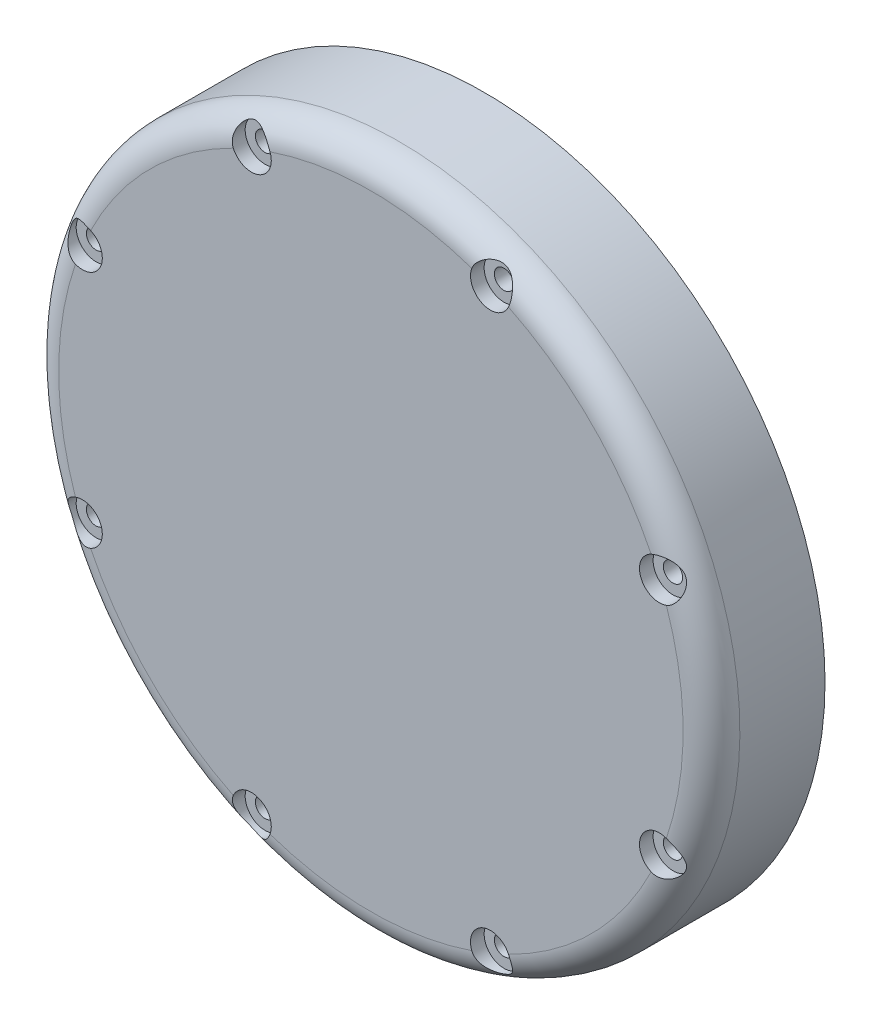
SolidWorks part; units mm, degrees
material "7075-O (SS)"
ref_plane "Front" through (0, 0, 0) normal (0, 0, 1) x (1, 0, 0)
ref_plane "Top" through (0, 0, 0) normal (0, 1, 0) x (1, 0, 0)
ref_plane "Right" through (0, 0, 0) normal (1, 0, 0) x (0, 0, -1)
sketch "Croquis1" plane through (0, 0, 0) normal (0, 0, 1) x (1, 0, 0)
  line L0 (-15, -49.8498) -> (-15, -54.0833)
  line L1 (15, -49.8498) -> (15, -54.0833)
  line L2 (-15, -47.697) -> (15, -47.697) construction
  line L3 (0, -50) -> (0, 50) construction
  arc A0 (18.9474, -56.9298) -> (-18.9474, -56.9298) centre (0, 0) ccw
  arc A1 (16.9811, -47.0281) -> (-16.9811, -47.0281) centre (0, 0) ccw
  arc A2 (15, -54.0833) -> (18.9474, -56.9298) centre (18, -54.0833) ccw
  arc A3 (-15, -54.0833) -> (-18.9474, -56.9298) centre (-18, -54.0833) cw
  arc A4 (15, -49.8498) -> (16.9811, -47.0281) centre (18, -49.8498) cw
  arc A5 (-15, -49.8498) -> (-16.9811, -47.0281) centre (-18, -49.8498) ccw
  point P8 (0, -47.697)
  dimension "D1" = 120
  dimension "D2" = 100
  dimension "D4" = 3
  dimension "D3" = 30
extrude "Saliente-Extruir1" add sketch "Croquis1" along normal blind 15
sketch "Croquis2" plane through (0, 0, 15) normal (0, 0, 1) x (1, 0, 0)
  circle A0 centre (0, 0) radius 60
  dimension "D1" = 120
extrude "Saliente-Extruir2" add sketch "Croquis2" along normal blind 5
hole_wizard "Refrentado para tornillo con cabeza troncocónica de M31" positions "Croquis3" profile "Croquis5" counterbore size "M3" standard "Ansi Metric" end condition up to next
sketch "Croquis3" plane through (0, 0, 20) normal (0, 0, 1) x (1, 0, 0)
  line L1 (-21.0476, -50.8134) -> (21.0476, 50.8134) construction
  line L4 (0, -50) -> (0, 50) construction
  point P4 (21.0476, 50.8134)
  point P18 (50.8134, 21.0476)
  point P19 (50.8134, -21.0476)
  point P20 (21.0476, -50.8134)
  point P21 (-21.0476, -50.8134)
  point P22 (-50.8134, -21.0476)
  point P23 (-50.8134, 21.0476)
  point P24 (-21.0476, 50.8134)
  dimension "D1" = 22.5
  dimension "D2" = 110
  dimension "D3" = 8
sketch "Croquis5" plane through (-21.0476, 50.8134, 20) normal (1, 0, 0) x (0, -1, 0)
  line L0 (0, 0) -> (0, 20)
  line L1 (0, 20) -> (1.7, 20)
  line L3 (1.7, 20) -> (1.7, 2.4)
  line L4 (1.7, 2.4) -> (3.5, 2.4)
  line L5 (3.5, 2.4) -> (3.5, 0)
  line L7 (3.5, 0) -> (0, 0)
  line L11 (0, -6.35) -> (0, 107.95) construction
  dimension "Diámetro de taladro hasta el siguiente" = 3.4
  dimension "Profundidad de taladro hasta el siguiente" = 20
  dimension "Diámetro de refrentado" = 7
  dimension "Profundidad de refrentado" = 2.4
sketch "Croquis6" plane through (0, 0, 0) normal (1, 0, 0) x (0, 0, -1)
  line L0 (40.5, 22.0023) -> (40.5, 0) construction
  line L1 (40.5, 0) -> (62.5023, 0) construction
  line L2 (-20, 60) -> (-20, -60) construction
  dimension "D1" = 60.5
fillet "Redondeo1" radius 5 1 edges at (60, 0, 20)
